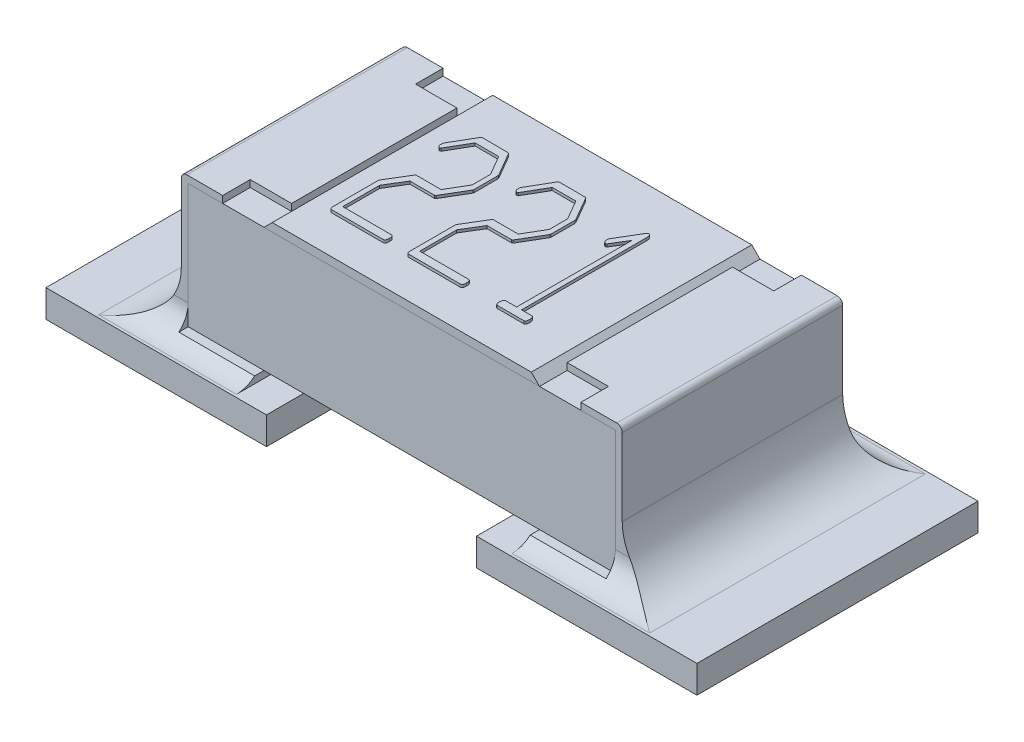
SolidWorks part; units mm, degrees
material "Ceramic Porcelain"
ref_plane "Front Plane" through (0, 0, 0) normal (0, 0, 1) x (1, 0, 0)
ref_plane "Top Plane" through (0, 0, 0) normal (0, 1, 0) x (1, 0, 0)
ref_plane "Right Plane" through (0, 0, 0) normal (1, 0, 0) x (0, 0, -1)
sketch "Sketch1" plane through (0, 0, 0) normal (1, 0, 0) x (0, 0, -1)
  line L0 (0, 55) -> (0, -55) construction
  line L1 (-0.4, 0.575) -> (0.4, 0.575)
  line L2 (-0.4, 0.575) -> (-0.4, 0.125)
  line L3 (-0.4, 0.125) -> (0.4, 0.125)
  line L4 (0.4, 0.575) -> (0.4, 0.125)
  line L5 (55, 0) -> (-55, 0) construction
  dimension "D1" = 0.8
  dimension "D2" = 0.4
  dimension "D3" = 0.45
  dimension "D4" = 0.125
extrude "Boss-Extrude1" add sketch "Sketch1" along normal mid plane 1.55
sketch "Sketch2" plane through (0, 0, 0) normal (0, 0, 1) x (1, 0, 0)
  line L0 (-0.5, 0.6) -> (-0.78, 0.6)
  line L1 (-0.8, 0.58) -> (-0.8, 0.1)
  line L2 (-0.8, 0.1) -> (-0.5, 0.1)
  line L3 (-0.5, 0.1) -> (-0.5, 0.125)
  line L4 (0.775, 0.125) -> (-0.775, 0.125) construction
  line L5 (-0.5, 0.125) -> (-0.775, 0.125)
  line L6 (-0.775, 0.125) -> (-0.775, 0.575)
  line L7 (-0.775, 0.575) -> (-0.5, 0.575)
  line L8 (0.775, 0.575) -> (-0.775, 0.575) construction
  line L9 (-0.5, 0.575) -> (-0.5, 0.6)
  line L11 (0.5, 0.575) -> (0.5, 0.6)
  line L12 (0.5, 0.6) -> (0.78, 0.6)
  line L13 (0.8, 0.58) -> (0.8, 0.1)
  line L14 (0.8, 0.1) -> (0.5, 0.1)
  line L15 (0.5, 0.1) -> (0.5, 0.125)
  line L16 (0.5, 0.125) -> (0.775, 0.125)
  line L17 (0.775, 0.125) -> (0.775, 0.575)
  line L18 (0.775, 0.575) -> (0.5, 0.575)
  arc A0 (0.78, 0.6) -> (0.8, 0.58) centre (0.78, 0.58) cw
  arc A1 (-0.78, 0.6) -> (-0.8, 0.58) centre (-0.78, 0.58) ccw
  point P28 (-0.8, 0.6)
  dimension "D6" = 0.02
  dimension "D1" = 0.025
  dimension "D2" = 0.025
  dimension "D3" = 0.025
  dimension "D4" = 0.3
  dimension "D5" = 0.3
extrude "Boss-Extrude2" add sketch "Sketch2" along normal mid plane 0.8 separate body
sketch "Sketch3" plane through (0, 0.6, 0) normal (0, 1, 0) x (1, 0, 0)
  line L0 (0.5, -0.4) -> (0.5, 0.4) construction
  line L1 (-0.5, 0.4) -> (-0.65, 0.4)
  line L2 (-0.5, 0.4) -> (-0.5, 0.3)
  line L3 (-0.5, 0.3) -> (-0.65, 0.3)
  line L4 (-0.65, 0.4) -> (-0.65, 0.3)
  line L5 (-0.5, -0.4) -> (-0.65, -0.4)
  line L6 (-0.5, -0.4) -> (-0.5, -0.3)
  line L7 (-0.5, -0.3) -> (-0.65, -0.3)
  line L8 (-0.65, -0.4) -> (-0.65, -0.3)
  line L9 (0.5, -0.4) -> (0.65, -0.4)
  line L10 (0.5, -0.4) -> (0.5, -0.3)
  line L11 (0.5, -0.3) -> (0.65, -0.3)
  line L12 (0.65, -0.4) -> (0.65, -0.3)
  line L13 (0.775, -0.4) -> (-0.775, -0.4) construction
  line L15 (0.5, 0.4) -> (0.65, 0.4)
  line L16 (0.5, 0.4) -> (0.5, 0.3)
  line L17 (0.5, 0.3) -> (0.65, 0.3)
  line L18 (0.65, 0.4) -> (0.65, 0.3)
  dimension "D1" = 0.15
  dimension "D2" = 0.1
extrude "Cut-Extrude1" cut sketch "Sketch3" against normal blind 0.025
sketch "Sketch4" plane through (0, 0, 0) normal (0, 0, 1) x (1, 0, 0)
  line L0 (-0.5, 0.575) -> (0.5, 0.575)
  line L1 (0.5, 0.575) -> (0.47, 0.605)
  line L2 (0.47, 0.605) -> (-0.47, 0.605)
  line L3 (-0.47, 0.605) -> (-0.5, 0.575)
  dimension "D1" = 45
  dimension "D2" = 45
  dimension "D3" = 0.03
extrude "Boss-Extrude3" add sketch "Sketch4" along normal mid plane 0.8 separate body
sketch "Sketch6" plane through (0, 0.605, 0) normal (0, 1, 0) x (1, 0, 0)
  line L0 (-0.4, -0.25) -> (0.4, -0.25) construction
  line L1 (0, -0.2777) -> (0, 0.2777) construction
  line L2 (-0.2777, 0) -> (0.2777, 0) construction
  line L3 (-0.47, -0.4) -> (-0.47, 0.4) construction
  line L4 (0.47, 0.4) -> (-0.47, 0.4) construction
  text T0 "221" font "SWMono" height 0.5
  dimension "D1" = 0.8
  dimension "D2" = 0.4
  dimension "D3" = 0.25
extrude "Boss-Extrude4" add sketch "Sketch6" along normal blind 0.01
sketch "Sketch7" plane through (0, 0, 0) normal (0, 1, 0) x (1, 0, 0)
  line L0 (0, -0.2833) -> (0, 0.2833) construction
  line L1 (-0.381, -0.51) -> (-1.181, -0.51)
  line L2 (-0.381, -0.51) -> (-0.381, 0.51)
  line L3 (-0.381, 0.51) -> (-1.181, 0.51)
  line L4 (-1.181, -0.51) -> (-1.181, 0.51)
  line L5 (0.381, -0.51) -> (1.181, -0.51)
  line L6 (0.381, -0.51) -> (0.381, 0.51)
  line L7 (0.381, 0.51) -> (1.181, 0.51)
  line L8 (1.181, -0.51) -> (1.181, 0.51)
  line L9 (-0.2833, 0) -> (0.2833, 0) construction
  dimension "D1" = 0.8
  dimension "D2" = 0.381
  dimension "D3" = 0.381
  dimension "D4" = 1.02
  dimension "D5" = 0.51
extrude "Boss-Extrude5" add sketch "Sketch7" along normal blind 0.1
fillet "Fillet3" radius 0.2 1 edges at (-0.8, 0.1, 0)
fillet "Fillet4" radius 0.2 1 edges at (0.8, 0.1, 0)
fillet "Fillet5" radius 0.1 2 edges at (0.75, 0.1, -0.4) (0.75, 0.1, 0.4)
fillet "Fillet6" radius 0.1 2 edges at (-0.75, 0.1, 0.4) (-0.75, 0.1, -0.4)
